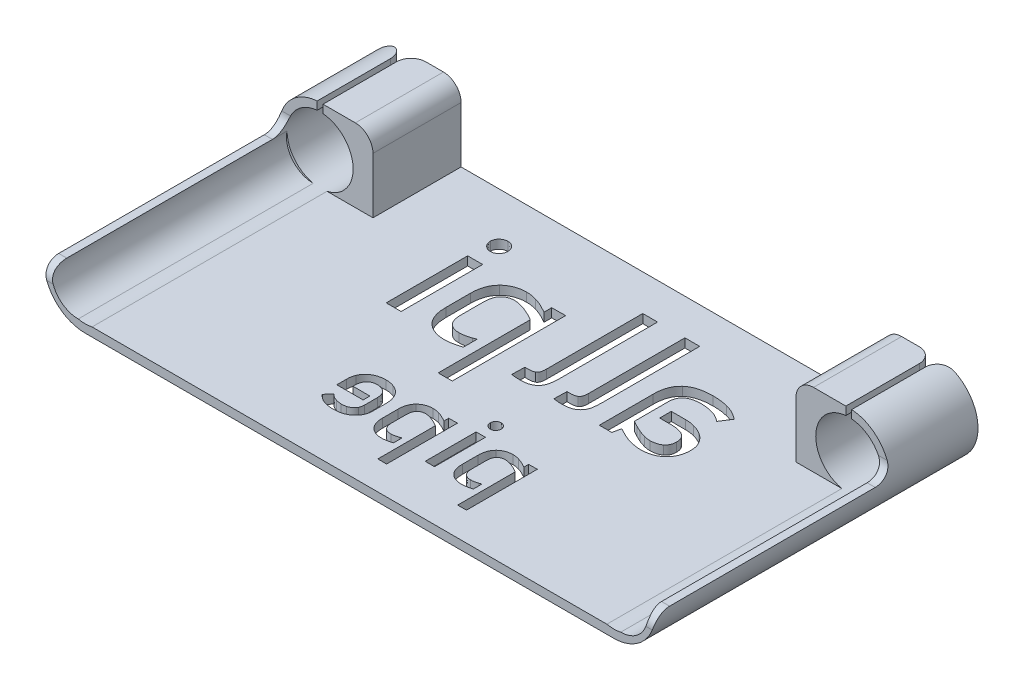
SolidWorks part; units mm, degrees
ref_plane "Front Plane" through (0, 0, 0) normal (0, 0, 1) x (1, 0, 0)
ref_plane "Top Plane" through (0, 0, 0) normal (0, 1, 0) x (1, 0, 0)
ref_plane "Right Plane" through (0, 0, 0) normal (1, 0, 0) x (0, 0, -1)
sketch "Sketch1" plane through (0, 0, 0) normal (0, 0, 1) x (1, 0, 0)
  line L0 (0, 0) -> (180, 0) construction
  line L1 (180, -14) -> (0, -14)
  line L2 (0, 14) -> (12, 14)
  line L3 (25, -11) -> (155, -11)
  line L4 (18, 8) -> (18, -5)
  line L5 (180, 14) -> (168, 14)
  line L6 (162, 8) -> (162, -5)
  line L7 (156, -11) -> (155, -11)
  line L8 (24, -11) -> (25, -11)
  line L9 (24, -11) -> (18, -11)
  line L10 (18, -11) -> (18, -5)
  line L11 (156, -11) -> (162, -11)
  line L12 (162, -11) -> (162, -5)
  circle A0 centre (0, 0) radius 11.25
  circle A1 centre (180, 0) radius 11.25
  arc A2 (0, 14) -> (0, -14) centre (0, 0) ccw
  arc A3 (180, -14) -> (180, 14) centre (180, 0) ccw
  arc A4 (12, 14) -> (18, 8) centre (12, 8) cw
  arc A6 (168, 14) -> (162, 8) centre (168, 8) ccw
  point P19 (18, -11)
  point P22 (162, 14)
  dimension "D1" = 22.5
  dimension "D2" = 22.5
  dimension "D4" = 28
  dimension "D9" = 6
  dimension "D3" = 180
  dimension "D5" = 3
  dimension "D6" = 130
  dimension "D7" = 18
  dimension "D8" = 18
extrude "Boss-Extrude1" add sketch "Sketch1" along normal blind 110
sketch "Sketch3" plane through (0, -14, 0) normal (0, -1, 0) x (-1, 0, 0)
  line L0 (-180, -55) -> (0, -55) construction
  line L1 (-180, -110) -> (-180, 0) construction
  line L2 (0, -110) -> (0, 0) construction
  text T0 "allpi\r\n" font "SWRomnd" height in points 120
extrude "Cut-Extrude1" cut sketch "Sketch3" against normal blind 10
sketch "Sketch4" plane through (0, -14, 0) normal (0, -1, 0) x (1, 0, 0)
  line L0 (180, 93.5485) -> (0, 93.5485) construction
  line L1 (180, 110) -> (180, 0) construction
  line L2 (0, 110) -> (0, 0) construction
  text T0 "pipe" font "SWRomnd" height in points 80
extrude "Cut-Extrude2" cut sketch "Sketch4" against normal blind 10
sketch "Sketch5" plane through (0, 0, 110) normal (0, 0, 1) x (1, 0, 0)
  line L0 (162, -11) -> (182.3585, -11)
  line L1 (191.25, 0) -> (194, 0)
  line L2 (180, 14) -> (162, 14)
  line L3 (162, 14) -> (162, -11)
  circle A0 centre (180, 0) radius 11.25 construction
  arc A1 (182.3585, -11) -> (191.25, 0) centre (182.3585, -1.9064) ccw
  arc A2 (180, -14) -> (180, 14) centre (180, 0) ccw construction
  arc A3 (194, 0) -> (180, 14) centre (180, 0) ccw
extrude "Cut-Extrude3" cut sketch "Sketch5" against normal blind 80
ref_plane "Plane1" through (90, 0, 0) normal (1, 0, 0) x (0, 0, -1)
mirror "Mirror1" about plane through (90, 0, 0) normal (1, 0, 0) of "Cut-Extrude3"
fillet "Fillet1" radius 5 2 edges at (-12.625, 0, 110) (192.625, 0, 110)
fillet "Fillet2" radius 5 2 edges at (-12.625, 0, 30) (192.625, 0, 30)
sketch "Sketch6" plane through (0, -14, 0) normal (0, -1, 0) x (-1, 0, 0)
  line L0 (-119.8939, -109.8189) -> (-56.2264, -110)
  line L1 (0, -110) -> (-180, -110) construction
  circle A0 centre (-87.9192, -60.3618) radius 58.893
extrude "Boss-Extrude2" add sketch "Sketch6" against normal up to surface (3 mm away) contours L0 A0 region at (87.9133, -14, 58.3121) up to face at (98.3868, -11, 86.9952)
sketch "Sketch7" plane through (0, -14, 0) normal (0, -1, 0) x (1, 0, 0)
  line L0 (180, 52.83) -> (0, 52.83) construction
  line L1 (180, 110) -> (180, 0) construction
  line L2 (0, 110) -> (0, 0) construction
  text T0 "allpi" font "LaserCut" height 40
extrude "Cut-Extrude4" cut sketch "Sketch7" against normal blind 13
sketch "Sketch8" plane through (0, -14, 0) normal (0, -1, 0) x (-1, 0, 0)
  line L0 (-180, -92.9077) -> (0, -92.9077) construction
  line L1 (-180, -110) -> (-180, 0) construction
  line L2 (0, -110) -> (0, 0) construction
  text T0 "pipe" font "LaserCut" height 25
extrude "Cut-Extrude5" cut sketch "Sketch8" against normal blind 13
sketch "Sketch10" plane through (0, 14, 0) normal (0, 1, 0) x (1, 0, 0)
  line L0 (0, 0) -> (0, -30)
  line L1 (180, 0) -> (180, -30)
extrude "Cut-Extrude-Thin3" cut sketch "Sketch10" against normal blind 13 and the other way through all thin contours L1 thin type mid plane wall 2
fillet "Fillet3" radius 5 2 edges at (179, 12.6027, 0) (181, 12.5849, 0)
mirror "Mirror2" about plane through (90, 0, 0) normal (1, 0, 0) of "Fillet3", "Cut-Extrude-Thin3"
